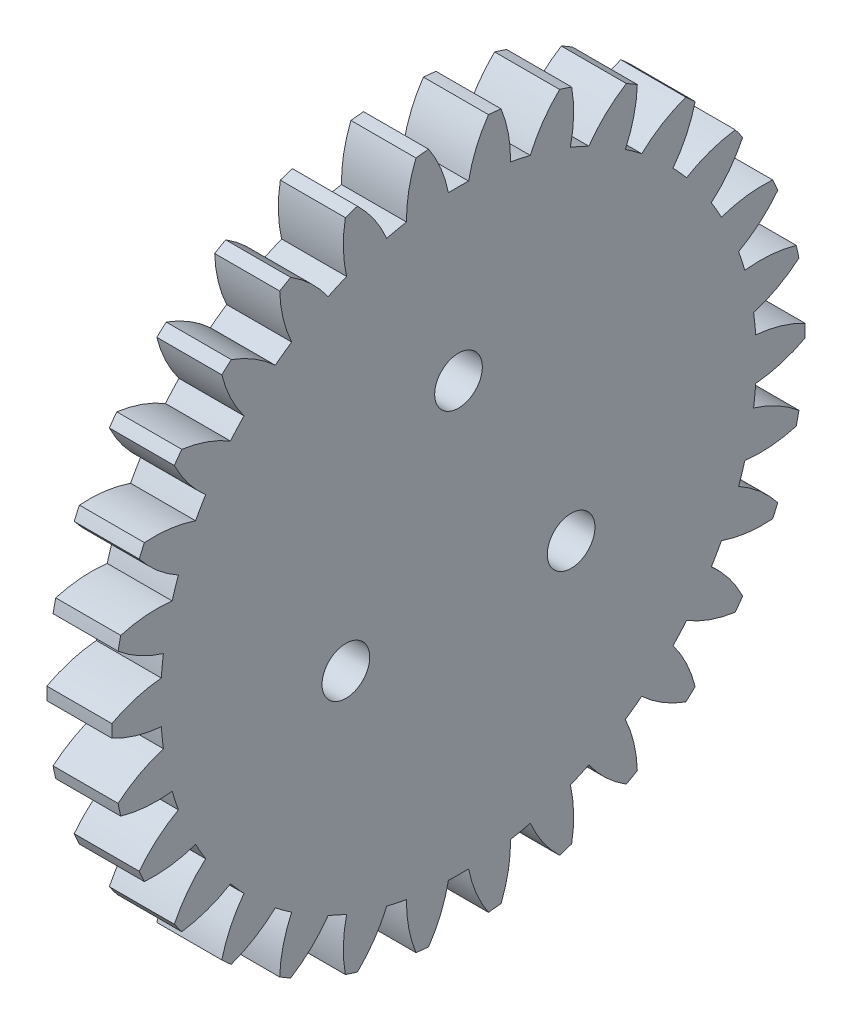
SolidWorks part; units mm, degrees
material "ﾎﾟﾘｵｷｼﾒﾁﾚﾝ(POM)ｱｾﾀｰﾙ共重合体"
ref_plane "Plane1" through (0, 0, 0) normal (0, 0, 1) x (1, 0, 0)
ref_plane "Plane2" through (0, 0, 0) normal (0, 1, 0) x (1, 0, 0)
ref_plane "Plane3" through (0, 0, 0) normal (1, 0, 0) x (0, 0, -1)
other "Configuration Table"
sketch "HoldingSke" plane through (0, 0, 0) normal (0, 1, 0) x (1, 0, 0)
  line L0 (0, 0) -> (0.866, -0.5)
  line L1 (-15, 0) -> (100, 0) construction
  line L2 (0, 0) -> (-2.1039, 2.3779)
  line L3 (0, 0) -> (-11.863, 4.5341)
  line L4 (0, 0) -> (7.479, 4.318)
  line L5 (0, 0) -> (-46.8476, -17.4728)
  line L6 (0, 0) -> (-2.4869, -1.6779)
  line L7 (-2.1039, 2.3779) -> (8.6586, 51.2059)
  line L8 (-76.2, 54.61) -> (-75.2, 54.61)
  line L9 (-71.009, 38.7566) -> (-53.1078, 45.2721)
  line L10 (-76.2, 71.12) -> (104.1128, 71.12)
  line L11 (0, 0) -> (-3, 0)
  line L12 (-76.2, 101.6) -> (-76.162, 101.6)
  line L13 (24.9733, 27.94) -> (52.9518, 28.4284)
  line L14 (24.9733, 27.94) -> (24.9743, 27.94)
  line L15 (24.9733, 27.94) -> (100.4006, 29.5858)
  line L16 (-63.627, -1) -> (-12.827, -1)
  circle A0 centre (0, 0) radius 4
  circle A1 centre (0, 0) radius 13.749
  circle A2 centre (0, 0) radius 37.5
  circle A3 centre (0, 0) radius 4
  dimension "MHD" = 27.498
  dimension "Hub_dia" = 75
  dimension "Bore" = 8
  dimension "MBD" = 8
  dimension "Num_teeth" = 30
  dimension "Pitch" = 1
  dimension "Overall_len" = 50
  dimension "Show_teeth" = 30
  dimension "Thickness" = 3
  dimension "OAL" = 50.0001
  dimension "T_dim" = 1
  dimension "Ap" = 20
  dimension "H" = 19.05
  dimension "Pitch_radius" = 180.3128
  dimension "Width" = 3
  dimension "Backlash" = 0.038
  dimension "Addendum_fac" = 1
  dimension "Dedendum_fac" = 1.25
  dimension "Clearance_fac" = 0.25
  dimension "Dedendum_add" = 0.001
  dimension "Module" = 1
sketch "BasProSke" plane through (0, 0, 0) normal (0, 1, 0) x (1, 0, 0)
  line L0 (-10, 0) -> (60, 0) construction
  line L1 (0, 0) -> (0, 16)
  line L2 (0, 0) -> (3, 0)
  line L3 (3, 0) -> (3, 16)
  line L4 (3, 16) -> (0, 16)
  dimension "Thickness" = 3
  dimension "Diameter" = 32
revolve "Base-Revolve" add sketch "BasProSke" angle 360 about L0
sketch "TooCutSke" plane through (0, 0, 0) normal (1, 0, 0) x (0, 0, -1)
  line L1 (0, 0) -> (0, 107) construction
  line L2 (0, 0) -> (-0.8515, 14.9758) construction
  line L3 (0, 0) -> (-3.1323, 29.8014) construction
  line L4 (-0.8515, 14.9758) -> (-1.5661, 14.9007) construction
  arc A0 (0.4664, 13.7411) -> (-0.4664, 13.7411) centre (0, 0) ccw
  arc A1 (1.3975, 15.9644) -> (-1.3975, 15.9644) centre (0, 0) ccw
  circle A2 centre (0, 0) radius 15 construction
  circle A3 centre (0, 0) radius 14.0954 construction
  arc A4 (-0.4664, 13.7411) -> (-1.3975, 15.9644) centre (-6.3534, 12.5823) ccw
  arc A5 (1.3975, 15.9644) -> (0.4664, 13.7411) centre (6.3534, 12.5823) ccw
  dimension "Root_dia" = 27.498
  dimension "Overcut_dia" = 32.0508
  dimension "Pitch_dia" = 30
  dimension "Base_dia" = 28.1908
  dimension "Flank_rad" = 6
  dimension "Half_ang" = 6
  dimension "Half_CT" = 0.7185
extrude "ToothCut" cut sketch "TooCutSke" along normal through all
fillet "Breaks" [suppressed] radius 0.02 tangent propagation no
fillet "RootFillets" [suppressed] radius 0.251
pattern_circular "TeethCuts" count 30 every 12 about axis through (-10, 0, 0) along (1, 0, 0) of "ToothCut", "RootFillets", "Breaks"
sketch "HubNeaOneSke" plane through (0, 0, 0) normal (-1, 0, 0) x (0, 0, 1)
  circle A0 centre (0, 0) radius 13.749
  dimension "Diameter" = 27.498
extrude "HubNearOne" [suppressed] add sketch "HubNeaOneSke" along normal blind 47.0001
sketch "HubNeaBotSke" plane through (0, 0, 0) normal (-1, 0, 0) x (0, 0, 1)
  circle A0 centre (0, 0) radius 13.749
  dimension "Diameter" = 27.498
extrude "HubNearBoth" [suppressed] add sketch "HubNeaBotSke" along normal blind 23.5
ref_plane "FarPln" through (3, 0, 0) normal (1, 0, 0) x (0, 0, -1)
sketch "HubFarSke" plane through (3, 0, 0) normal (1, 0, 0) x (0, 0, -1)
  circle A0 centre (0, 0) radius 13.749
  dimension "Diameter" = 27.498
extrude "HubFar" [suppressed] add sketch "HubFarSke" along normal blind 23.5
sketch "BorSke" plane through (0, 0, 0) normal (1, 0, 0) x (0, 0, -1)
  circle A0 centre (0, 0) radius 4
  dimension "Diameter" = 8
extrude "Bore" cut sketch "BorSke" along normal mid plane 100.0001
sketch "KeySke" plane through (0, 0, 0) normal (1, 0, 0) x (0, 0, -1)
  line L0 (-1, 0) -> (-1, 5)
  line L1 (-1, 5) -> (1, 5)
  line L2 (1, 5) -> (1, 0)
  line L3 (0, 0) -> (0, 34) construction
  line L4 (-1, 0) -> (1, 0)
  dimension "Offset" = 5
  dimension "Width" = 2
extrude "Keyway" [suppressed] cut sketch "KeySke" along normal mid plane 100.0001
pattern_circular "Keyway2" [suppressed] count 2 every 90 about axis through (-10, 0, 0) along (1, 0, 0) reverse direction yes
sketch "ｽｹｯﾁ1" plane through (0, 0, 0) normal (-1, 0, 0) x (0, 0, 1)
  circle A0 centre (0, 0) radius 4 construction
  circle A1 centre (0, 0) radius 4
extrude "ﾎﾞｽ - 押し出し1" add sketch "ｽｹｯﾁ1" against normal up to surface (3 mm away) up to face at (3, 0, 4)
sketch "ｽｹｯﾁ2" plane through (0, 0, 0) normal (-1, 0, 0) x (0, 0, 1)
  circle A0 centre (0, 0) radius 6 construction
  circle A1 centre (0, 6) radius 1.1
  circle A2 centre (5.1962, -3) radius 1.1
  circle A3 centre (-5.1962, -3) radius 1.1
  point P5 (-5.8258, -1.4353)
  point P6 (3.9941, -2.8784)
  point P11 (0, 0)
  point P12 (0, 0)
  point P13 (0, 0)
  dimension "D1" = 12
  dimension "D2" = 2.2
  dimension "D3" = 3
extrude "ｶｯﾄ - 押し出し1" cut sketch "ｽｹｯﾁ2" against normal through all
equation "' \"Module@HoldingSke\" = 6.35"
equation "' \"Num_teeth@HoldingSke\" = 12"
equation "' \"Ap@HoldingSke\" =  20"
equation "' \"Ap@HoldingSke\" = 20"
equation "' \"Width@HoldingSke\" = 0.5 * 25.4"
equation "' \"Hub_dia@HoldingSke\"= 1 * 25.4"
equation "' \"Hub_dia@HoldingSke\" = 1 * 25.4"
equation "' \"Overall_len@HoldingSke\" = 1.0 * 25.4"
equation "' \"Bore@HoldingSke\" = 0.75 * 25.4"
equation "' \"T_dim@HoldingSke\" = 0.1 * 25.4"
equation "' \"Width@KeySke\" = 0.25 * 25.4"
equation "' \"Show_teeth@HoldingSke\" = 13"
equation "' \"Backlash@HoldingSke\" = 0.009 * 25.4"
equation "' \"Addendum_fac@HoldingSke\" = 1.0"
equation "' \"Dedendum_fac@HoldingSke\" = 1.25"
equation "' \"Dedendum_add@HoldingSke\" = 0.00005 * 25.4"
equation "' \"Clearance_fac@HoldingSke\" = 0.25"
equation "\"Pitch@HoldingSke\" = 1 / \"Module@HoldingSke\""
equation "\"Overcut_dia@TooCutSke\" = (\"Num_teeth@HoldingSke\" + 2 * \"Addendum_fac@HoldingSke\") / \"Pitch@HoldingSke\" + 0.002 * 25.4"
equation "\"Pitch_dia@TooCutSke\" = \"Num_teeth@HoldingSke\" / \"Pitch@HoldingSke\""
equation "\"Base_dia@TooCutSke\" = \"Num_teeth@HoldingSke\" / \"Pitch@HoldingSke\" * cos((\"Ap@HoldingSke\"  * 3.14159265 / 180))"
equation "\"Root_dia@TooCutSke\" = (\"Num_teeth@HoldingSke\" + 2) / \"Pitch@HoldingSke\" - 2 * (\"Addendum_fac@HoldingSke\" + \"Dedendum_fac@HoldingSke\") / \"Pitch@HoldingSke\" - \"Dedendum_add@HoldingSke\" * 2"
equation "\"Half_ang@TooCutSke\" = 180 / \"Num_teeth@HoldingSke\""
equation "\"Half_CT@TooCutSke\" = \"Num_teeth@HoldingSke\" / \"Pitch@HoldingSke\" * sin((3.14159265 / 2 / \"Num_teeth@HoldingSke\")) / 2 - 7 * \"Backlash@HoldingSke\" / 4"
equation "\"Flank_rad@TooCutSke\" = \"Num_teeth@HoldingSke\" / \"Pitch@HoldingSke\" / 5"
equation "\"Radius@RootFillets\" = \"Clearance_fac@HoldingSke\" / \"Pitch@HoldingSke\" + \"Dedendum_add@HoldingSke\""
equation "\"Break_rad@Breaks\" = 0.02 / \"Pitch@HoldingSke\""
equation "\"Thickness@HoldingSke\" = \"Width@HoldingSke\""
equation "\"OAL@HoldingSke\" = \"Thickness@HoldingSke\""
equation "\"MHD@HoldingSke\" = (\"Num_teeth@HoldingSke\" + 2) / \"Pitch@HoldingSke\" - 2 * (\"Addendum_fac@HoldingSke\" + \"Dedendum_fac@HoldingSke\")  / \"Pitch@HoldingSke\" - \"Dedendum_add@HoldingSke\" * 2"
equation "\"MBD@HoldingSke\" = (\"Num_teeth@HoldingSke\" + 2) / \"Pitch@HoldingSke\" - 2 * (\"Addendum_fac@HoldingSke\" + \"Dedendum_fac@HoldingSke\")  / \"Pitch@HoldingSke\" - \"Dedendum_add@HoldingSke\" * 2 - 0.002 * 25.4"
equation "\"MHD@HoldingSke\" = ((sgn( \"MHD@HoldingSke\" - \"Hub_dia@HoldingSke\" )-1)*( \"MHD@HoldingSke\" - \"Hub_dia@HoldingSke\" ))/-2+ \"Hub_dia@HoldingSke\""
equation "\"MBD@HoldingSke\" = ((sgn( \"MBD@HoldingSke\" - \"Bore@HoldingSke\" )-1)*( \"MBD@HoldingSke\" - \"Bore@HoldingSke\" ))/-2+ \"Bore@HoldingSke\""
equation "\"OAL@HoldingSke\" = ((sgn( \"OAL@HoldingSke\" - \"Overall_len@HoldingSke\" )+1)*( \"OAL@HoldingSke\" - \"Overall_len@HoldingSke\" ))/2 + \"Overall_len@HoldingSke\" + 0.000002 * 25.4"
equation "\"Num_teeth@TeethCuts\" = int( \"Show_teeth@HoldingSke\" ) + 1"
equation "\"Num_teeth@TeethCuts\" = ((sgn( \"Num_teeth@TeethCuts\" - \"Num_teeth@HoldingSke\" )-1)*( \"Num_teeth@TeethCuts\" - \"Num_teeth@HoldingSke\" ))/-2+ \"Num_teeth@HoldingSke\""
equation "\"Num_teeth@TeethCuts\" = ((sgn( \"Num_teeth@TeethCuts\" - 2.0)+1)*( \"Num_teeth@TeethCuts\" - 2.0))/2 +2.0"
equation "\"Angle@TeethCuts\" = 360.0 / \"Num_teeth@HoldingSke\""
equation "\"Diameter@BasProSke\" = (\"Num_teeth@HoldingSke\" + 2 * \"Addendum_fac@HoldingSke\") / \"Pitch@HoldingSke\""
equation "\"Thickness@BasProSke\"  = \"Thickness@HoldingSke\""
equation "' \"Fillet_rad@BasProSke\" =  \"Thickness@HoldingSke\" * 0.05"
equation "' \"Fillet_rad@BasProSke\" = \"Thickness@HoldingSke\" * 0.05"
equation "\"MHD@HoldingSke\" = ((sgn( \"MHD@HoldingSke\" - \"Root_dia@TooCutSke\" )-1)*( \"MHD@HoldingSke\" - \"Root_dia@TooCutSke\" ))/-2+ \"Root_dia@TooCutSke\""
equation "\"Diameter@HubNeaOneSke\" = \"MHD@HoldingSke\""
equation "\"Length@HubNearOne\" = \"OAL@HoldingSke\" - \"Thickness@BasProSke\""
equation "\"Diameter@HubNeaBotSke\" = \"MHD@HoldingSke\""
equation "\"Length@HubNearBoth\" = ( \"OAL@HoldingSke\" - \"Thickness@BasProSke\" ) / 2.0"
equation "\"Thickness@FarPln\" = \"Thickness@BasProSke\""
equation "\"Diameter@HubFarSke\" = \"MHD@HoldingSke\""
equation "\"Length@HubFar\" = ( \"OAL@HoldingSke\" - \"Thickness@BasProSke\" ) / 2.0"
equation "\"Diameter@BorSke\" = \"MBD@HoldingSke\""
equation "\"D1@Bore\" = \"OAL@HoldingSke\" * 2.0"
equation "\"D1@Keyway\" = \"OAL@HoldingSke\" * 2.0"
equation "\"Offset@KeySke\" = \"T_dim@HoldingSke\" + \"MBD@HoldingSke\" / 2.0"
